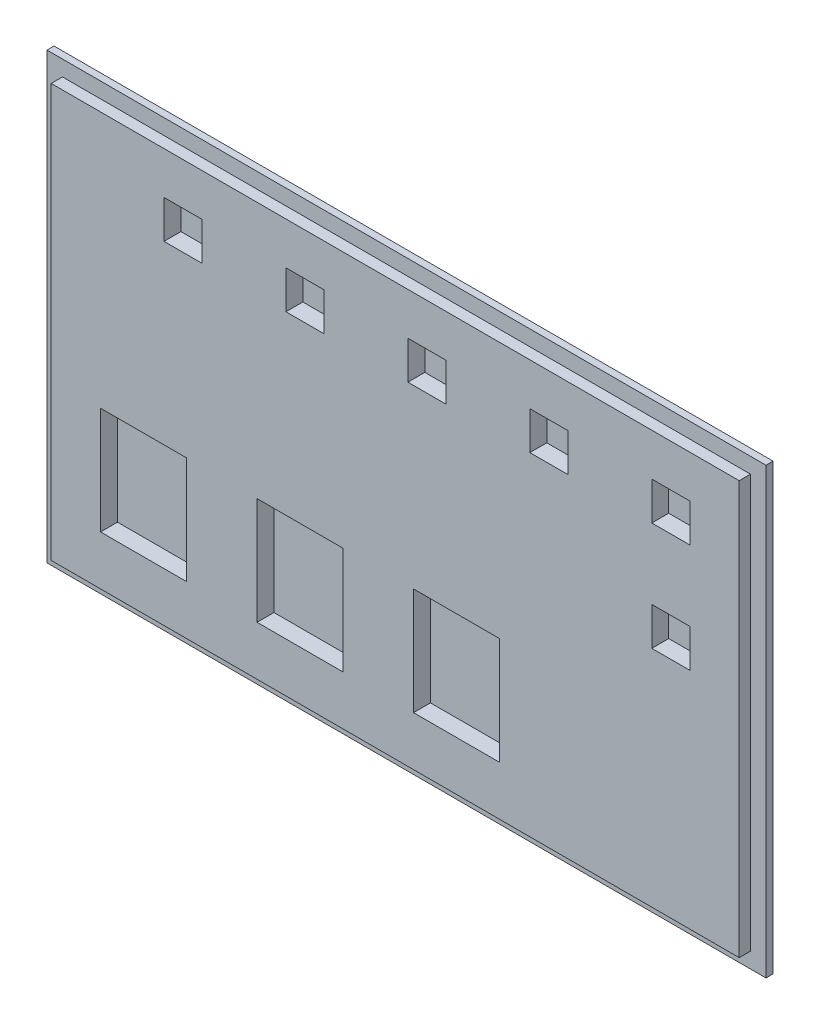
SolidWorks part; units mm, degrees
ref_plane "Přední rovina" through (0, 0, 0) normal (0, 0, 1) x (1, 0, 0)
ref_plane "Horní rovina" through (0, 0, 0) normal (0, 1, 0) x (1, 0, 0)
ref_plane "Pravá rovina" through (0, 0, 0) normal (1, 0, 0) x (0, 0, -1)
sketch "Skica1" plane through (0, 0, 0) normal (0, 0, 1) x (1, 0, 0)
  line L1 (0, 0) -> (102, 0)
  line L2 (0, 0) -> (0, 63)
  line L3 (0, 63) -> (102, 63)
  line L4 (102, 0) -> (102, 63)
  line L25 (18.2, 54.8) -> (23.6, 54.8)
  line L26 (18.2, 54.8) -> (18.2, 49.4)
  line L27 (18.2, 49.4) -> (23.6, 49.4)
  line L28 (23.6, 54.8) -> (23.6, 49.4)
  line L29 (35.5, 54.8) -> (40.9, 54.8)
  line L30 (35.5, 54.8) -> (35.5, 49.4)
  line L31 (35.5, 49.4) -> (40.9, 49.4)
  line L32 (40.9, 54.8) -> (40.9, 49.4)
  line L33 (52.8, 54.8) -> (58.2, 54.8)
  line L34 (52.8, 54.8) -> (52.8, 49.4)
  line L35 (52.8, 49.4) -> (58.2, 49.4)
  line L36 (58.2, 54.8) -> (58.2, 49.4)
  line L37 (70.1, 54.8) -> (75.5, 54.8)
  line L38 (70.1, 54.8) -> (70.1, 49.4)
  line L39 (70.1, 49.4) -> (75.5, 49.4)
  line L40 (75.5, 54.8) -> (75.5, 49.4)
  line L41 (87.4, 54.8) -> (92.8, 54.8)
  line L42 (87.4, 54.8) -> (87.4, 49.4)
  line L43 (87.4, 49.4) -> (92.8, 49.4)
  line L44 (92.8, 54.8) -> (92.8, 49.4)
  line L45 (2.2, 60.8) -> (99.8, 60.8)
  line L46 (2.2, 60.8) -> (2.2, 2.2)
  line L47 (2.2, 2.2) -> (99.8, 2.2)
  line L48 (99.8, 60.8) -> (99.8, 2.2)
  line L49 (9.2, 24.4) -> (21.4, 24.4)
  line L50 (9.2, 24.4) -> (9.2, 9.2)
  line L51 (9.2, 9.2) -> (21.4, 9.2)
  line L52 (21.4, 24.4) -> (21.4, 9.2)
  line L53 (31.4, 24.4) -> (43.6, 24.4)
  line L54 (31.4, 24.4) -> (31.4, 9.2)
  line L55 (31.4, 9.2) -> (43.6, 9.2)
  line L56 (43.6, 24.4) -> (43.6, 9.2)
  line L57 (53.6, 24.4) -> (65.8, 24.4)
  line L58 (53.6, 24.4) -> (53.6, 9.2)
  line L59 (53.6, 9.2) -> (65.8, 9.2)
  line L60 (65.8, 24.4) -> (65.8, 9.2)
  line L63 (87.4, 39.4) -> (92.8, 39.4)
  line L65 (87.4, 39.4) -> (87.4, 34)
  line L66 (87.4, 34) -> (92.8, 34)
  line L67 (92.8, 39.4) -> (92.8, 34)
  point P29 (90.1, 54.8)
  point P42 (0, 0)
  point P43 (0, 0)
  dimension "D2" = 5.4
  dimension "D3" = 5.4
  dimension "D4" = 7
  dimension "D5" = 6
  dimension "D6" = 5.4
  dimension "D7" = 5.4
  dimension "D8" = 5.4
  dimension "D9" = 5.4
  dimension "D10" = 5.4
  dimension "D11" = 5.4
  dimension "D12" = 5.4
  dimension "D13" = 5.4
  dimension "D14" = 11.9
  dimension "D15" = 102
  dimension "D16" = 11.9
  dimension "D17" = 11.9
  dimension "D18" = 63
  dimension "D19" = 11.9
  dimension "D20" = 2.2
  dimension "D21" = 2.2
  dimension "D22" = 2.2
  dimension "D23" = 2.2
  dimension "D24" = 6
  dimension "D25" = 12.2
  dimension "D26" = 15.2
  dimension "D27" = 12.2
  dimension "D28" = 12.2
  dimension "D32" = 7
  dimension "D33" = 7
  dimension "D34" = 10
  dimension "D35" = 10
  dimension "D36" = 5.4
  dimension "D37" = 5.4
  dimension "D38" = 10
  dimension "D39" = 97.6
extrude "Přidat vysunutím1" add sketch "Skica1" along normal blind 2.6 contours L48 L45 L46 L47 L25 L28 L27 L26 L29 L32 L31 L30 L33 L36 L35 L34 L37 L40 L39 L38 L41 L44 L43 L42 L49 L52 L51 L50 L53 L56 L55 L54 L57 L60 L59 L58 region at (52.1455, 32.507, 0)
extrude "Přidat vysunutím2" add sketch "Skica1<3>" along normal blind 1 contours L1 L4 L3 L2 L45 L48 L47 L46 region at (1.1989, 31.5, 0)
sketch "Skica1<3>" plane through (0, 0, 0) normal (0, 0, 1) x (1, 0, 0) same geometry as "Skica1"
extrude "Přidat vysunutím3" add sketch "Skica1<5>" along normal blind 0.2 contours L58 L59 L60 | L54 L55 L56 | L52 L50 L51 | L67 L63 L65 L66 | L44 L41 L42 L43 | L40 L37 L38 L39 | L36 L33 L34 L35 | L32 L29 L30 L31 | L28 L25 L26 L27 region at (20.9, 52.1, 0) region at (38.2, 52.1, 0) region at (55.5, 52.1, 0) region at (72.8, 52.1, 0) region at (90.1, 52.1, 0) region at (15.3, 16.8, 0) region at (37.5, 16.8, 0) region at (59.7, 16.8, 0) region at (90.1, 36.7, 0)
sketch "Skica1<5>" plane through (0, 0, 0) normal (0, 0, 1) x (1, 0, 0) same geometry as "Skica1"
